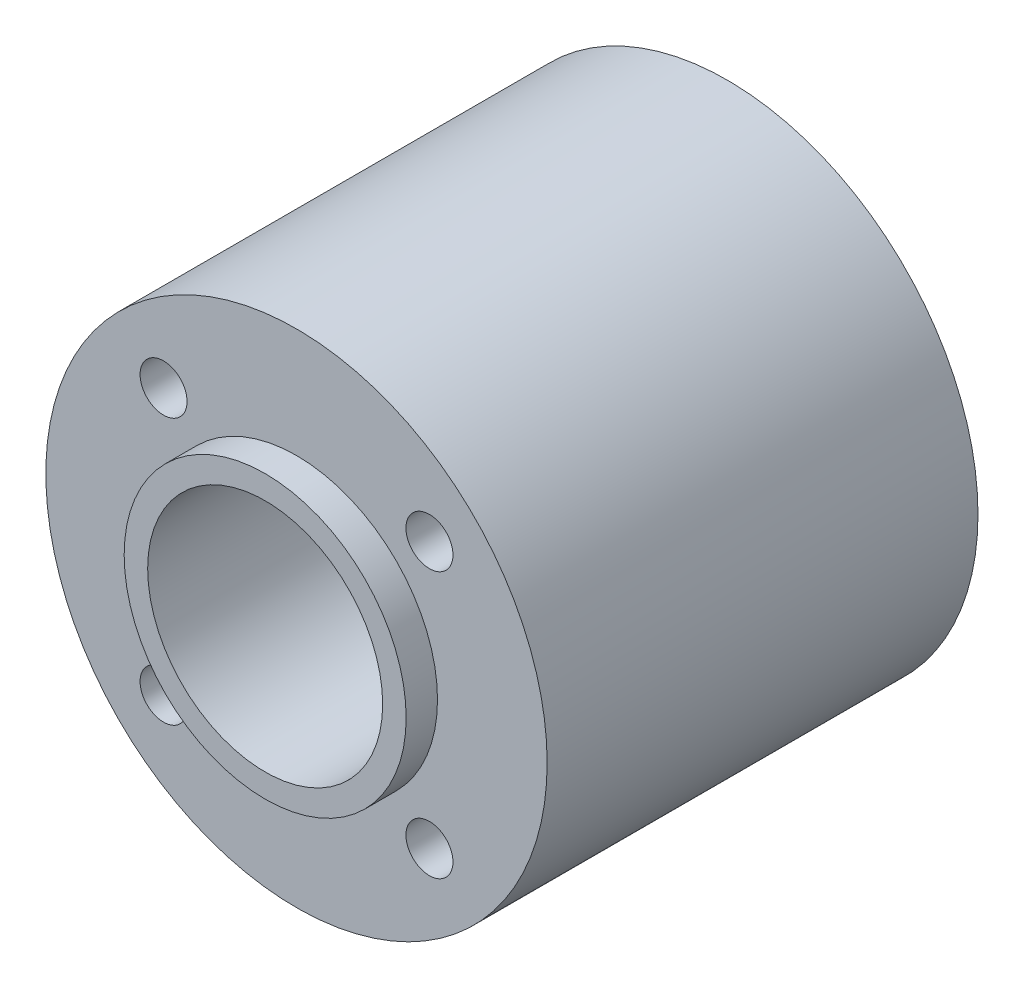
SolidWorks part; units mm, degrees
ref_plane "Front Plane" through (0, 0, 0) normal (0, 0, 1) x (1, 0, 0)
ref_plane "Top Plane" through (0, 0, 0) normal (0, 1, 0) x (1, 0, 0)
ref_plane "Right Plane" through (0, 0, 0) normal (1, 0, 0) x (0, 0, -1)
sketch "Sketch1" plane through (0, 0, 0) normal (0, 0, 1) x (1, 0, 0)
  circle A0 centre (0, 0) radius 16
  circle A1 centre (0, 0) radius 9
  circle A2 centre (0, 0) radius 7.5
  dimension "D1" = 32
  dimension "D2" = 18
  dimension "D3" = 15
extrude "Boss-Extrude1" add sketch "Sketch1" against normal blind 27.5 contours A0 A1 | A1 A2 region at (-15.5475, 0, 0) region at (-8.7454, 0, 0)
extrude "Boss-Extrude2" add sketch "Sketch1<3>" along normal blind 2 contours A1 A2 region at (-8.7454, 0, 0)
sketch "Sketch1<3>" plane through (0, 0, 0) normal (0, 0, 1) x (1, 0, 0) same geometry as "Sketch1"
extrude "Boss-Extrude3" add sketch "Sketch1<4>" against normal blind 2 from surface contours A1 A2 region at (-8.7454, 0, 0) starting at face at (16, 0, -27.5)
sketch "Sketch1<4>" plane through (0, 0, 0) normal (0, 0, 1) x (1, 0, 0) same geometry as "Sketch1"
sketch "Sketch2" plane through (0, 0, 0) normal (0, 0, 1) x (1, 0, 0)
  line L0 (0, 0) -> (0, 12) construction
  line L1 (0, 0) -> (-8.4853, 8.4853) construction
  circle A0 centre (0, 0) radius 12 construction
  circle A1 centre (-8.4853, 8.4853) radius 1.5
  circle A2 centre (8.4853, 8.4853) radius 1.5
  circle A3 centre (8.4853, -8.4853) radius 1.5
  circle A4 centre (-8.4853, -8.4853) radius 1.5
  circle A5 centre (0, 0) radius 9 construction
  point P15 (0, 0)
  dimension "D1" = 45
  dimension "D2" = 24
  dimension "D3" = 3
  dimension "D4" = 4
extrude "Cut-Extrude1" cut sketch "Sketch2" against normal through all
